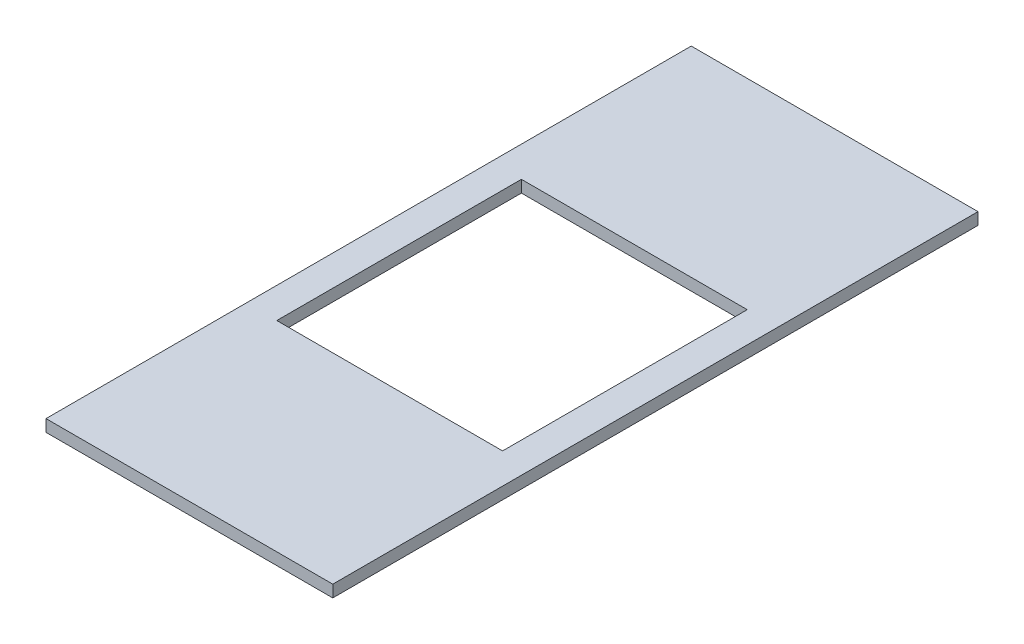
SolidWorks part; units mm, degrees
ref_plane "Front Plane" through (0, 0, 0) normal (0, 0, 1) x (1, 0, 0)
ref_plane "Top Plane" through (0, 0, 0) normal (0, 1, 0) x (1, 0, 0)
ref_plane "Right Plane" through (0, 0, 0) normal (1, 0, 0) x (0, 0, -1)
sketch "Sketch1" plane through (0, 0, 0) normal (0, 1, 0) x (1, 0, 0)
  line L1 (0, 0) -> (152.4, 0)
  line L2 (0, 0) -> (0, 342.9)
  line L3 (0, 342.9) -> (152.4, 342.9)
  line L4 (152.4, 0) -> (152.4, 342.9)
  line L5 (16.2, 236.45) -> (136.2, 236.45)
  line L6 (16.2, 236.45) -> (16.2, 106.45)
  line L7 (16.2, 106.45) -> (136.2, 106.45)
  line L8 (136.2, 236.45) -> (136.2, 106.45)
  point P4 (76.2, 236.45)
  point P10 (76.2, 342.9)
  point P11 (136.2, 171.45)
  point P12 (152.4, 171.45)
  dimension "D1" = 342.9
  dimension "D2" = 152.4
  dimension "D3" = 120
  dimension "D4" = 130
extrude "Boss-Extrude1" add sketch "Sketch1" along normal blind 6.35
